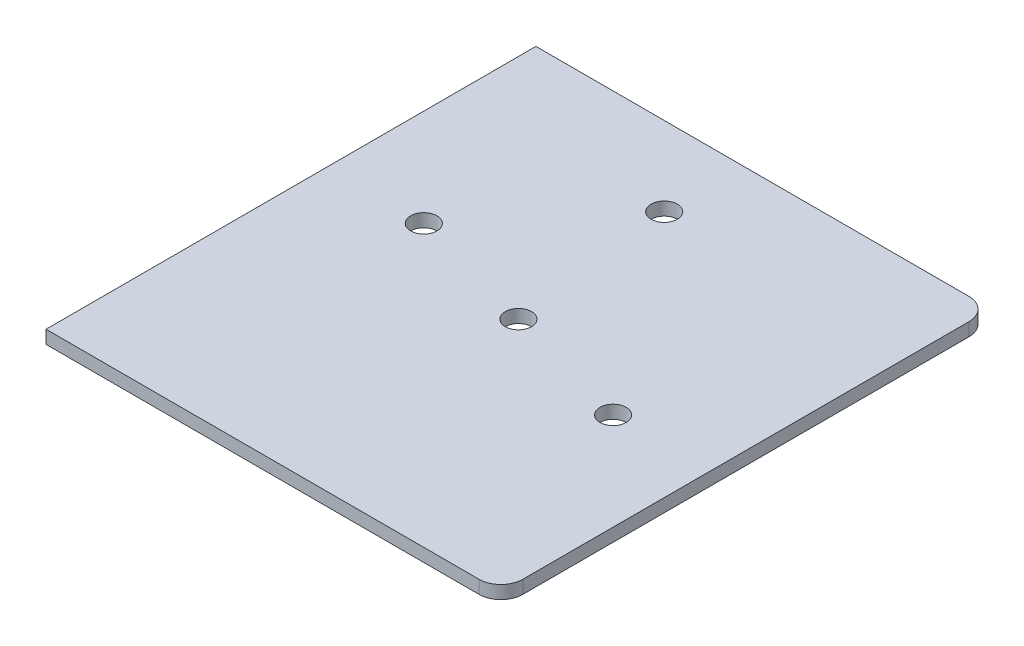
SolidWorks part; units mm, degrees
material "Oak"
ref_plane "Front Plane" through (0, 0, 0) normal (0, 0, 1) x (1, 0, 0)
ref_plane "Top Plane" through (0, 0, 0) normal (0, 1, 0) x (1, 0, 0)
ref_plane "Right Plane" through (0, 0, 0) normal (1, 0, 0) x (0, 0, -1)
sketch "Sketch1" plane through (0, 0, 0) normal (0, 1, 0) x (1, 0, 0)
  line L0 (558.8, 99.2707) -> (461.5124, 17.6367)
  line L1 (-558.8, -177.8) -> (558.8, -177.8)
  line L2 (-558.8, 177.8) -> (558.8, 177.8)
  line L3 (558.8, -177.8) -> (558.8, 177.8)
  line L4 (-558.8, -177.8) -> (558.8, 177.8) construction
  line L5 (-558.8, 177.8) -> (558.8, -177.8) construction
  line L6 (-228.6, 177.8) -> (228.6, 177.8)
  line L7 (-228.6, -177.8) -> (228.6, -177.8)
  line L8 (228.6, 177.8) -> (228.6, -177.8)
  line L9 (-228.6, 177.8) -> (228.6, -177.8) construction
  line L10 (-228.6, -177.8) -> (228.6, 177.8) construction
  line L11 (228.6, -177.8) -> (558.8, 99.2707)
  line L12 (-228.6, 177.8) -> (-228.6, -177.8)
  point P4 (0, 0)
extrude "Boss-Extrude1" add sketch "Sketch1" along normal blind 9.525 contours L8 L11 L0 L3 L2 region at (358.5765, 0, -54.5316)
extrude "Boss-Extrude2" add sketch "Sketch1<4>" along normal blind 9.525 contours L11 L1 L3 L0 region at (448.7333, 0, 85.4431)
sketch "Sketch1<4>" plane through (0, 0, 0) normal (0, 1, 0) x (1, 0, 0) same geometry as "Sketch1"
sketch "Sketch3" plane through (0, 0, 0) normal (0, -1, 0) x (1, 0, 0)
  line L0 (558.8, 177.8) -> (228.6, -177.8)
  line L1 (228.6, 177.8) -> (558.8, -177.8)
  line L2 (228.6, -177.8) -> (393.7, -177.8)
  line L3 (228.6, -177.8) -> (558.8, -177.8) construction
  line L4 (393.7, 0) -> (393.7, -177.8)
  line L5 (393.7, 0) -> (228.6, 0)
  line L6 (228.6, -177.8) -> (228.6, 177.8) construction
  line L7 (393.7, 0) -> (558.8, 0)
  line L8 (228.6, 0) -> (228.6, 177.8)
  line L9 (558.8, 177.8) -> (558.8, -177.8) construction
  line L10 (311.15, 44.45) -> (311.15, 0)
  line L15 (311.15, -88.9) -> (393.7, -88.9)
  line L16 (228.6, 177.8) -> (228.6, -177.8)
  line L17 (228.6, -177.8) -> (558.8, -177.8)
  line L18 (476.25, 88.9) -> (311.15, 88.9)
  line L19 (311.15, 88.9) -> (311.15, 44.45)
  line L20 (558.8, -177.8) -> (558.8, 177.8)
  line L21 (558.8, 177.8) -> (228.6, 177.8)
  line L22 (228.6, 177.8) -> (228.6, -177.8)
  line L23 (228.6, -177.8) -> (558.8, -177.8)
  line L24 (558.8, -177.8) -> (558.8, 177.8)
  line L25 (228.6, 177.8) -> (558.8, 177.8) construction
  line L26 (558.8, 177.8) -> (228.6, 177.8)
  line L33 (311.15, -177.8) -> (476.25, 177.8)
  circle A0 centre (393.7, 0) radius 9.525
  circle A1 centre (379.0811, -120.4326) radius 9.525
  circle A2 centre (299.1573, -25.8555) radius 9.525
  circle A3 centre (488.2427, 25.8555) radius 9.525
  dimension "D1" = 162.026
  dimension "D2" = 137.121
  dimension "D3" = 137.121
  dimension "D4" = 98.0145
  dimension "D5" = 65.095
  dimension "D6" = 0
extrude "Cut-Extrude6" cut sketch "Sketch3" along direction (0, 1, 0) on the side against the normal through all contours A3 | L7 A0 L0 | L0 A0 L33 | L33 A0 L1 | L1 A0 L5 | L5 A0 L0 | L0 A0 L33 | L33 A0 L4 | L4 A0 L1 | L1 A0 L7 | A1 | A2 region at (399.358, 0, 2.4673) region at (397.2264, 0, 5.2495) region at (399.358, 0, -2.4673) region at (390.1736, 0, -5.2495) region at (388.042, 0, 2.4673) region at (395.9673, 0, -5.7736) region at (388.042, 0, -2.4673) region at (392.3415, 0, -6.1519) region at (392.7649, 0, 5.9126) region at (379.0811, 0, -120.4326) region at (299.1573, 0, -25.8555) region at (488.2427, 0, 25.8555)
fillet "Fillet1" radius 15.875 2 edges at (558.8, 4.7625, 177.8) (558.8, 4.7625, -177.8)
